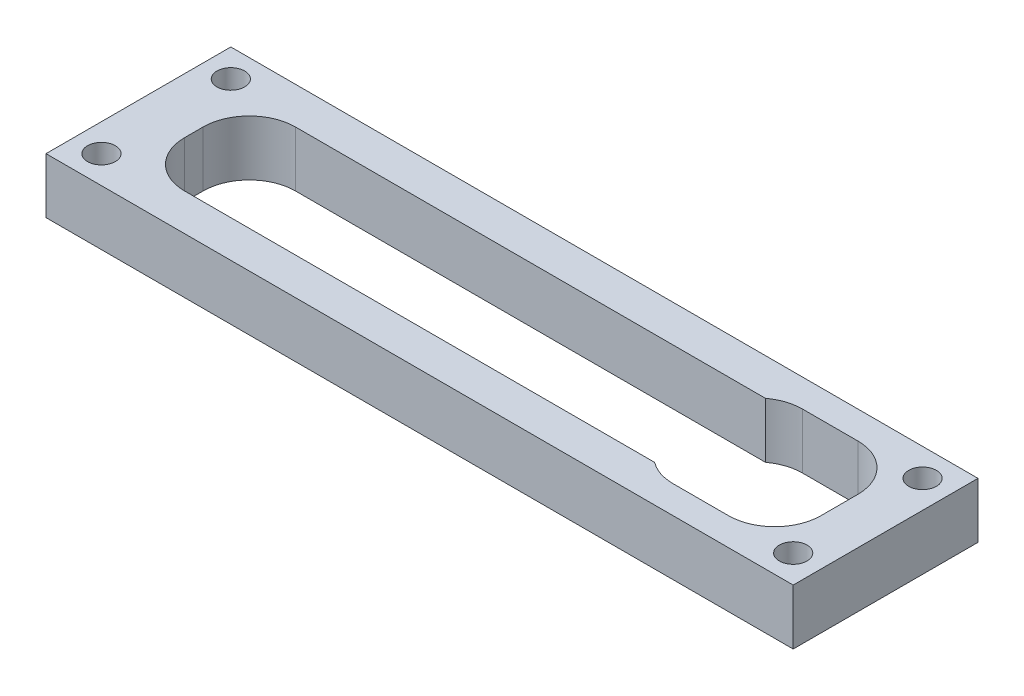
SolidWorks part; units mm, degrees
ref_plane "Front Plane" through (0, 0, 0) normal (0, 0, 1) x (1, 0, 0)
ref_plane "Top Plane" through (0, 0, 0) normal (0, 1, 0) x (1, 0, 0)
ref_plane "Right Plane" through (0, 0, 0) normal (1, 0, 0) x (0, 0, -1)
sketch "Sketch1" plane through (0, 0, 0) normal (0, 1, 0) x (1, 0, 0)
  line L0 (40.4319, 20) -> (40.4319, 0) construction
  line L1 (0, 0) -> (80.8639, 0)
  line L2 (0, 0) -> (0, 20)
  line L3 (0, 20) -> (80.8639, 20)
  line L4 (80.8639, 0) -> (80.8639, 20)
  line L5 (0, 10) -> (80.8639, 10) construction
  line L6 (40.4319, 16) -> (40.4319, 4) construction
  line L7 (6, 16) -> (74.8639, 16)
  line L8 (6, 16) -> (6, 4)
  line L9 (6, 4) -> (74.8639, 4)
  line L10 (74.8639, 16) -> (74.8639, 4)
  line L11 (6, 10) -> (74.8639, 10) construction
  circle A0 centre (3, 17) radius 1.5
  circle A1 centre (3, 3) radius 1.5
  circle A2 centre (77.8639, 3) radius 1.5
  circle A3 centre (77.8639, 17) radius 1.5
  point P17 (40.4319, 10)
  point P18 (40.4319, 10)
  dimension "D7" = 3
  dimension "D1" = 80.8639
  dimension "D2" = 20
  dimension "D3" = 68.8639
  dimension "D4" = 12
  dimension "D5" = 3
  dimension "D6" = 3
extrude "Boss-Extrude1" add sketch "Sketch1" along normal blind 6
sketch "Sketch2" plane through (0, 6, 0) normal (0, 1, 0) x (1, 0, 0)
  line L0 (92, 10) -> (-49908, 10) construction
  line L1 (74.8639, 4) -> (74.8639, 16) construction
  line L2 (61.8639, 17) -> (61.8639, 16)
  line L5 (74.8639, 16) -> (6, 16) construction
  line L6 (68.8639, 17) -> (68.8639, 3) construction
  line L7 (61.8639, 17) -> (75.8639, 17)
  line L9 (61.8639, 3) -> (75.8639, 3)
  line L10 (75.8639, 17) -> (75.8639, 3)
  line L12 (61.8639, 16) -> (74.8639, 16)
  line L13 (74.8639, 16) -> (74.8639, 4)
  line L14 (74.8639, 4) -> (61.8639, 4)
  line L15 (6, 4) -> (74.8639, 4) construction
  line L16 (61.8639, 4) -> (61.8639, 3)
  point P4 (74.8639, 10)
  point P23 (68.8639, 10)
  dimension "D1" = 1
  dimension "D2" = 14
  dimension "D3" = 14
extrude "Cut-Extrude1" cut sketch "Sketch2" against normal through all
fillet "Fillet1" radius 5 6 edges at (75.8639, 3, -17) (75.8639, 3, -3) (61.8639, 3, -17) (61.8639, 3, -3) (6, 3, -4) (6, 3, -16)
equation "\"TrackLength\"= ( ( \"n\" * 28 ) ) / cos ( \"MountAngle\" ) - ( 2 * \"x\" )"
equation "\"D1@Sketch1\"=\"TrackLength\""
equation "\"TrackWidth\"= \"MarbleTrackWidth\" + ( 2 * 4 )"
equation "\"D2@Sketch1\"=\"TrackWidth\""
equation "\"MarbleTrackWidth\"= \"MarbleWidth\" - 1"
equation "\"MarbleTrackLength\"= \"TrackLength\" - ( 2 * 6 )"
equation "\"D3@Sketch1\"=\"MarbleTrackLength\""
equation "\"D4@Sketch1\"=\"MarbleTrackWidth\""
equation "\"MarbleWidth\"= 13"
equation "\"n\"= 3"
equation "\"MountAngle\" = 10"
equation "\"x\"= 14 / cos ( \"MountAngle\" ) - 12"
